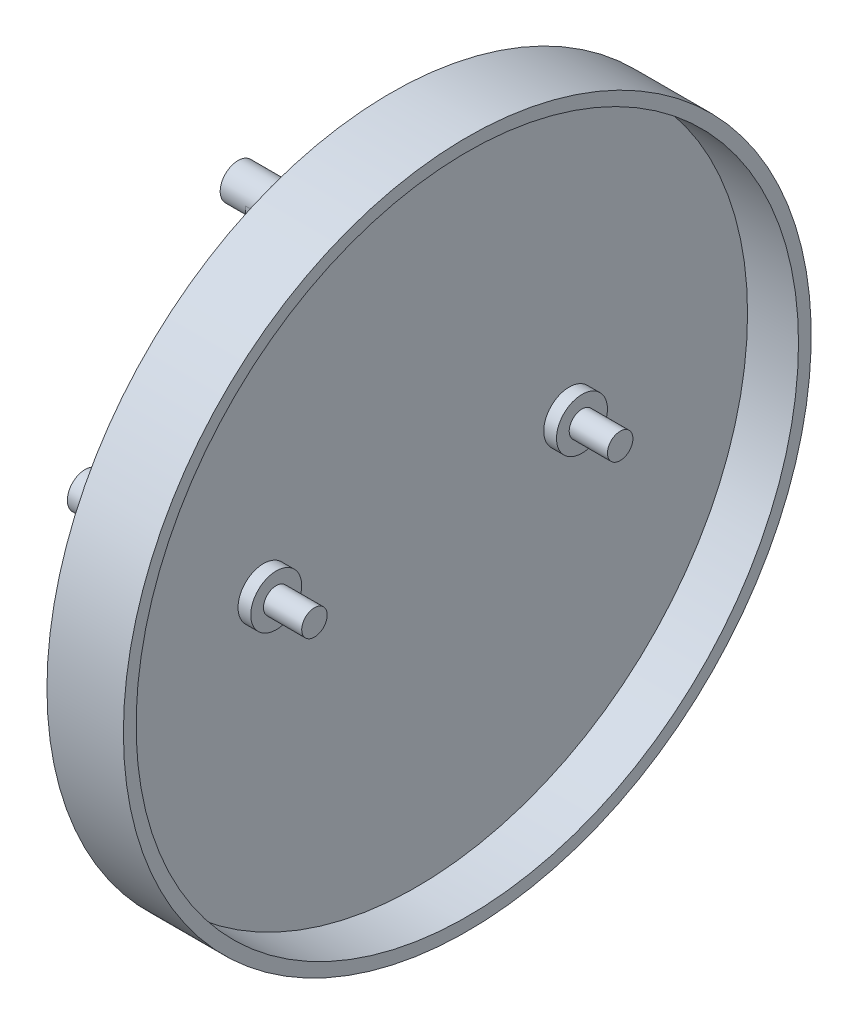
SolidWorks part; units mm, degrees
ref_plane "Front Plane" through (0, 0, 0) normal (0, 0, 1) x (1, 0, 0)
ref_plane "Top Plane" through (0, 0, 0) normal (0, 1, 0) x (1, 0, 0)
ref_plane "Right Plane" through (0, 0, 0) normal (1, 0, 0) x (0, 0, -1)
sketch "Sketch2" plane through (0, 0, 0) normal (1, 0, 0) x (0, 0, -1)
  line L0 (0, -1.778) -> (30.48, -1.778)
  line L1 (0, 1.778) -> (30.48, 1.778)
  arc A0 (0, 1.778) -> (0, -1.778) centre (0, 0) ccw
  arc A1 (30.48, -1.778) -> (30.48, 1.778) centre (30.48, 0) ccw
  dimension "D1" = 3.556
  dimension "D2" = 3.556
  dimension "D3" = 30.48
extrude "Boss-Extrude1" add sketch "Sketch2" along normal blind 2.54
sketch "Sketch3" plane through (0, 0, 0) normal (-1, 0, 0) x (0, 0, 1)
  circle A0 centre (-30.48, 0) radius 1.778
  circle A1 centre (0, 0) radius 1.778
extrude "Boss-Extrude2" add sketch "Sketch3" along normal blind 2.54 and the other way blind 12.7
ref_plane "Plane4" through (12.7, 0, 0) normal (1, 0, 0) x (0, 0, -1)
sketch "Sketch4" plane through (12.7, 0, 0) normal (1, 0, 0) x (0, 0, -1)
  line L0 (30.48, 0) -> (0, 0) construction
  circle A0 centre (15.24, 0) radius 34.29
  point P2 (30.48, 0)
  point P4 (0, 0)
  point P10 (15.24, 0)
  dimension "D1" = 68.58
extrude "Boss-Extrude3" add sketch "Sketch4" along normal blind 7.62
sketch "Sketch5" plane through (0, 0, 0) normal (1, 0, 0) x (0, 0, -1)
  line L0 (30.48, 1.778) -> (0, 1.778) construction
  line L1 (0, -1.778) -> (30.48, -1.778) construction
  line L2 (13.462, -19.05) -> (13.462, 19.05)
  line L3 (17.018, 19.05) -> (17.018, -19.05)
  arc A0 (13.462, -19.05) -> (17.018, -19.05) centre (15.24, -19.05) ccw
  arc A1 (17.018, 19.05) -> (13.462, 19.05) centre (15.24, 19.05) ccw
  point P6 (15.24, 1.778)
  dimension "D1" = 3.556
  dimension "D2" = 3.556
  dimension "D3" = 38.1
  dimension "D4" = 17.272
  dimension "D5" = 17.272
extrude "Boss-Extrude4" add sketch "Sketch5" along normal blind 2.54
sketch "Sketch6" plane through (2.54, 0, 0) normal (1, 0, 0) x (0, 0, -1)
  circle A0 centre (15.24, -19.05) radius 1.778
  circle A1 centre (15.24, 19.05) radius 1.778
extrude "Boss-Extrude5" add sketch "Sketch6" along normal up to surface (10.16 mm away) and the other way blind 5.08 up to face at (12.7, 0, -28.702)
sketch "Sketch7" plane through (20.32, 0, 0) normal (1, 0, 0) x (0, 0, -1)
  circle A0 centre (15.24, 0) radius 33.02
  circle A1 centre (15.24, 0) radius 34.29 construction
  dimension "D1" = 66.04
extrude "Cut-Extrude1" cut sketch "Sketch7" against normal blind 5.08
sketch "Sketch9" plane through (15.24, 0, 0) normal (1, 0, 0) x (0, 0, -1)
  circle A0 centre (0, 0) radius 2.54
  circle A1 centre (30.48, 0) radius 2.54
  circle A3 centre (0, 0) radius 1.778 construction
  circle A4 centre (30.48, 0) radius 1.778 construction
  dimension "D1" = 5.08
  dimension "D2" = 5.08
extrude "Boss-Extrude6" add sketch "Sketch9" along normal blind 1.27
sketch "Sketch10" plane through (16.51, 0, 0) normal (1, 0, 0) x (0, 0, -1)
  circle A0 centre (30.48, 0) radius 1.27
  circle A1 centre (0, 0) radius 1.27
  circle A2 centre (0, 0) radius 2.54 construction
  circle A3 centre (30.48, 0) radius 2.54 construction
  dimension "D1" = 2.54
  dimension "D2" = 2.54
extrude "Boss-Extrude7" add sketch "Sketch10" along normal up to surface (3.81 mm away) up to face at (20.32, 0, -48.26)
